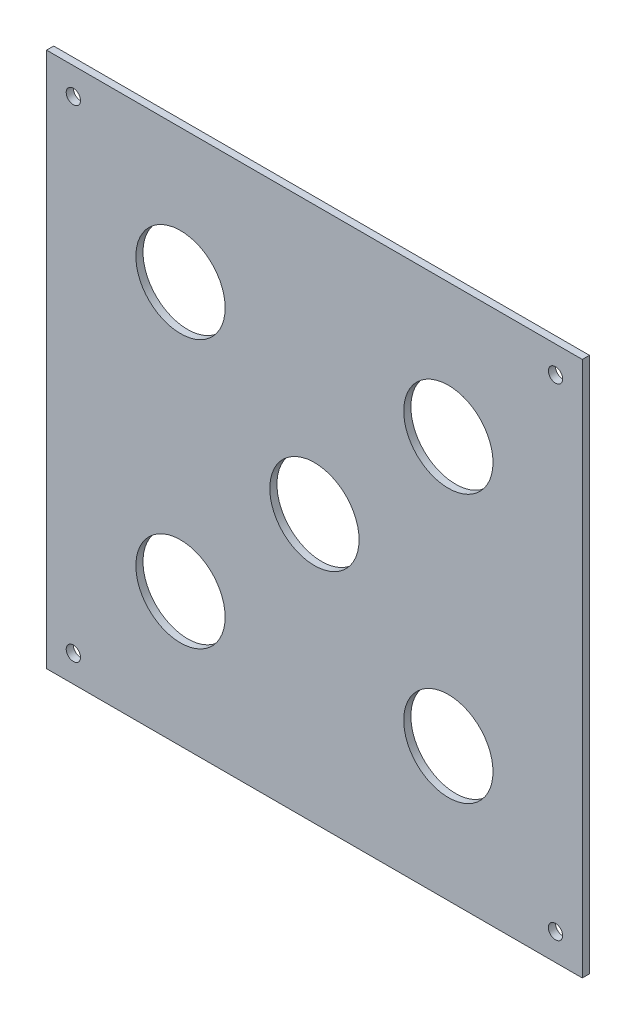
SolidWorks part; units mm, degrees
ref_plane "Alzado" through (0, 0, 0) normal (0, 0, 1) x (1, 0, 0)
ref_plane "Planta" through (0, 0, 0) normal (0, 1, 0) x (1, 0, 0)
ref_plane "Vista lateral" through (0, 0, 0) normal (1, 0, 0) x (0, 0, -1)
sketch "Croquis1" plane through (0, 0, 0) normal (0, 0, 1) x (1, 0, 0)
  line L1 (-75, -75) -> (75, -75)
  line L2 (-75, -75) -> (-75, 75)
  line L3 (-75, 75) -> (75, 75)
  line L4 (75, -75) -> (75, 75)
  line L5 (-75, -75) -> (75, 75) construction
  line L6 (-75, 75) -> (75, -75) construction
  point P0 (0, 0)
extrude "Saliente-Extruir1" add sketch "Croquis1" along normal blind 2
sketch "Croquis3" plane through (0, 0, 2) normal (0, 0, 1) x (1, 0, 0)
  line L1 (-67.5, -67.5) -> (67.5, -67.5)
  line L2 (-67.5, -67.5) -> (-67.5, 67.5)
  line L3 (-67.5, 67.5) -> (67.5, 67.5)
  line L4 (67.5, -67.5) -> (67.5, 67.5)
  line L5 (-67.5, -67.5) -> (67.5, 67.5) construction
  line L6 (-67.5, 67.5) -> (67.5, -67.5) construction
  line L7 (-37.5, -37.5) -> (37.5, -37.5)
  line L8 (-37.5, -37.5) -> (-37.5, 37.5)
  line L9 (-37.5, 37.5) -> (37.5, 37.5)
  line L10 (37.5, -37.5) -> (37.5, 37.5)
  line L11 (-37.5, -37.5) -> (37.5, 37.5) construction
  line L12 (-37.5, 37.5) -> (37.5, -37.5) construction
  circle A0 centre (-67.5, -67.5) radius 2
  circle A1 centre (67.5, -67.5) radius 2
  circle A2 centre (67.5, 67.5) radius 2
  circle A3 centre (-67.5, 67.5) radius 2
  circle A4 centre (-37.5, -37.5) radius 12.5
  circle A5 centre (37.5, -37.5) radius 12.5
  circle A6 centre (37.5, 37.5) radius 12.5
  circle A7 centre (-37.5, 37.5) radius 12.5
  circle A8 centre (0, 0) radius 12.5
  point P0 (0, 0)
  point P6 (0, 0)
  dimension "D1" = 2
  dimension "D3" = 2
  dimension "D2" = 2
  dimension "D4" = 2
extrude "Cortar-Extruir2" cut sketch "Croquis3" against normal blind 2 contours A7 | A6 | A5 | A4 | A8 | A1 | A2 | A3 | A0
